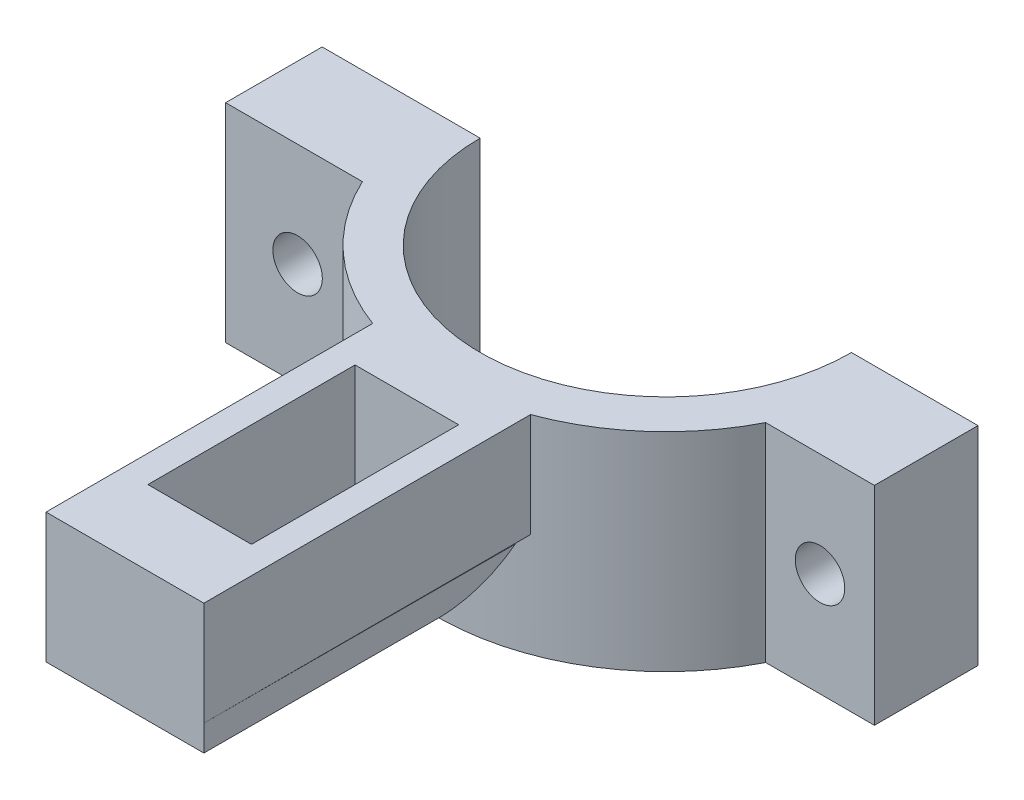
SolidWorks part; units mm, degrees
ref_plane "前基準面" through (0, 0, 0) normal (0, 0, 1) x (1, 0, 0)
ref_plane "上基準面" through (0, 0, 0) normal (0, 1, 0) x (1, 0, 0)
ref_plane "右基準面" through (0, 0, 0) normal (1, 0, 0) x (0, 0, -1)
sketch "草圖1" plane through (0, 0, 0) normal (0, 1, 0) x (1, 0, 0)
  circle A0 centre (0, 0) radius 14.34
  dimension "D1" = 28.68
extrude "伸長-薄件1" add sketch "草圖1" along normal blind 16.05 thin thin type one direction wall 3.29
ref_plane "平面1" through (17.75, 0, 0) normal (1, 0, 0) x (0, 0, -1)
sketch "草圖2" plane through (17.75, 0, 0) normal (1, 0, 0) x (0, 0, -1)
  line L0 (0, -983.95) -> (0, 49016.05) construction
  line L1 (14.34, 16.05) -> (-14.34, 16.05) construction
  line L2 (-1017.63, 8.025) -> (48982.37, 8.025) construction
  line L3 (-17.63, 16.05) -> (-17.63, 0) construction
  line L5 (-8, 16.05) -> (8, 16.05)
  line L6 (-8, 16.05) -> (-8, 0)
  line L7 (-8, 0) -> (8, 0)
  line L8 (8, 16.05) -> (8, 0)
  line L9 (-8, 16.05) -> (8, 0) construction
  line L10 (-8, 0) -> (8, 16.05) construction
  point P5 (0, 16.05)
  point P6 (0, 8.025)
  point P10 (-17.63, 8.025)
  dimension "D1" = 0
  dimension "D2" = 16
extrude "填料-伸長1" add sketch "草圖2" along normal blind 9.77 and the other way blind 3
sketch "草圖3" plane through (0, 16.05, 0) normal (0, 1, 0) x (1, 0, 0)
  line L0 (14.34, 0) -> (27.52, 0) construction
  line L1 (27.52, 8) -> (27.52, -8) construction
  line L2 (15.7104, -8) -> (27.52, -8) construction
  line L3 (27.52, 8) -> (24.11, 8)
  line L4 (27.52, 8) -> (27.52, -8)
  line L5 (27.52, -8) -> (24.11, -8)
  line L6 (24.11, 8) -> (24.11, -8)
  circle A0 centre (0, 0) radius 14.34 construction
  dimension "D1" = 3.41
extrude "除料-伸長1" cut sketch "草圖3" against normal through all
sketch "草圖4" plane through (0, 0, 8) normal (0, 0, 1) x (1, 0, 0)
  line L0 (19.9102, -983.95) -> (19.9102, 49016.05) construction
  line L1 (15.7104, 16.05) -> (24.11, 16.05) construction
  line L2 (-984.2896, 8.025) -> (49015.7104, 8.025) construction
  line L3 (15.7104, 0) -> (15.7104, 16.05) construction
  circle A0 centre (19.9102, 8.025) radius 1.91
  point P5 (19.9102, 16.05)
  point P10 (15.7104, 8.025)
  dimension "D1" = 3.82
extrude "除料-伸長2" cut sketch "草圖4" against normal through all
ref_plane "平面2" through (0, 0, 17.75) normal (0, 0, 1) x (1, 0, 0)
sketch "草圖5" plane through (0, 0, 17.75) normal (0, 0, 1) x (1, 0, 0)
  line L0 (-1017.63, 8.025) -> (48982.37, 8.025) construction
  line L1 (-17.63, 16.05) -> (-17.63, 0) construction
  line L2 (0, -983.95) -> (0, 49016.05) construction
  line L3 (14.34, 16.05) -> (-14.34, 16.05) construction
  line L5 (-6.095, 16.2886) -> (6.095, 16.2886)
  line L6 (-6.095, 16.2886) -> (-6.095, 8.025)
  line L7 (-6.095, 8.025) -> (6.095, 8.025)
  line L8 (6.095, 16.2886) -> (6.095, 8.025)
  line L9 (-6.095, 16.2886) -> (6.095, 8.025) construction
  line L10 (-6.095, 8.025) -> (6.095, 16.2886) construction
  point P5 (-17.63, 8.025)
  point P6 (0, 12.1568)
  point P10 (0, 16.05)
  dimension "D1" = 12.19
extrude "填料-伸長2" add sketch "草圖5" along normal blind 4 and the other way blind 2.77
sketch "草圖6" plane through (0, 16.2886, 0) normal (0, 1, 0) x (1, 0, 0)
  line L1 (-6.095, -14.98) -> (6.095, -14.98)
  line L2 (-6.095, -14.98) -> (-6.095, -21.75)
  line L3 (-6.095, -21.75) -> (6.095, -21.75)
  line L4 (6.095, -14.98) -> (6.095, -21.75)
extrude "填料-伸長3" add sketch "草圖6" along normal blind 63
sketch "草圖8" plane through (0, 79.2886, 0) normal (0, 1, 0) x (1, 0, 0)
  line L1 (-6.095, -21.75) -> (6.095, -21.75)
  line L2 (-6.095, -21.75) -> (-6.095, -14.98)
  line L3 (-6.095, -14.98) -> (6.095, -14.98)
  line L4 (6.095, -21.75) -> (6.095, -14.98)
extrude "填料-伸長4" add sketch "草圖8" along normal blind 0.16
ref_plane "平面3" through (-17.75, 0, 0) normal (1, 0, 0) x (0, 0, -1)
sketch "草圖12" plane through (-17.75, 0, 0) normal (1, 0, 0) x (0, 0, -1)
  line L0 (0.5435, -983.95) -> (0.5435, 49016.05) construction
  line L1 (17.63, 16.05) -> (-16.5429, 16.05) construction
  line L2 (-982.37, 8.025) -> (49017.63, 8.025) construction
  line L3 (17.63, 0) -> (17.63, 16.05) construction
  line L5 (8.5435, 16.05) -> (-7.4565, 16.05)
  line L6 (8.5435, 16.05) -> (8.5435, 0)
  line L7 (8.5435, 0) -> (-7.4565, 0)
  line L8 (-7.4565, 16.05) -> (-7.4565, 0)
  line L9 (8.5435, 16.05) -> (-7.4565, 0) construction
  line L10 (8.5435, 0) -> (-7.4565, 16.05) construction
  point P5 (0.5435, 16.05)
  point P6 (0.5435, 8.025)
  point P10 (17.63, 8.025)
  dimension "D1" = 0
  dimension "D2" = 16
extrude "填料-伸長5" add sketch "草圖12" along normal blind 3.16 and the other way blind 10
sketch "草圖13" plane through (0, 16.05, 0) normal (0, 1, 0) x (1, 0, 0)
  line L0 (-14.34, 0) -> (-27.75, 0) construction
  line L1 (-27.75, 8.5435) -> (-27.75, -7.4565) construction
  line L2 (-27.75, -7.4565) -> (-15.9755, -7.4565) construction
  line L3 (-27.75, 8.5435) -> (-26.54, 8.5435)
  line L4 (-27.75, 8.5435) -> (-27.75, -7.4565)
  line L5 (-27.75, -7.4565) -> (-26.54, -7.4565)
  line L6 (-26.54, 8.5435) -> (-26.54, -7.4565)
  circle A0 centre (0, 0) radius 14.34 construction
  dimension "D1" = 1.21
extrude "除料-伸長3" cut sketch "草圖13" against normal through all
sketch "草圖14" plane through (0, 0, -8.5435) normal (0, 0, -1) x (-1, 0, 0)
  line L0 (20.9808, -983.95) -> (20.9808, 49016.05) construction
  line L1 (26.54, 16.05) -> (15.4216, 16.05) construction
  line L2 (-973.46, 8.025) -> (49026.54, 8.025) construction
  line L3 (26.54, 0) -> (26.54, 16.05) construction
  circle A0 centre (20.9808, 8.025) radius 1.91
  point P5 (20.9808, 16.05)
  point P10 (26.54, 8.025)
  dimension "D1" = 3.82
extrude "除料-伸長4" cut sketch "草圖14" against normal through all
sketch "草圖15" plane through (0, 79.4486, 0) normal (0, 1, 0) x (1, 0, 0)
  line L0 (6.095, -14.98) -> (-6.095, -14.98) construction
  circle A0 centre (0, -14.98) radius 4.05
  dimension "D1" = 8.1
extrude "除料-伸長5" cut sketch "草圖15" against normal blind 24
sketch "草圖16" plane through (0, 16.05, 0) normal (0, 1, 0) x (1, 0, 0)
  line L0 (24.11, 8) -> (24.11, -8) construction
  line L1 (24.11, 0) -> (-32.2905, 0)
  line L2 (24.11, 0) -> (24.11, 19.935)
  line L3 (24.11, 19.935) -> (-32.2905, 19.935)
  line L4 (-32.2905, 0) -> (-32.2905, 19.935)
extrude "除料-伸長6" cut sketch "草圖16" against normal through all
sketch "草圖17" plane through (0, 0, 21.75) normal (0, 0, 1) x (1, 0, 0)
  line L1 (-6.095, 8.025) -> (6.095, 8.025)
  line L2 (-6.095, 8.025) -> (-6.095, 79.4486)
  line L3 (-6.095, 79.4486) -> (6.095, 79.4486)
  line L4 (6.095, 8.025) -> (6.095, 79.4486)
extrude "填料-伸長7" add sketch "草圖17" along normal blind 25
sketch "草圖18" plane through (-6.095, 0, 0) normal (-1, 0, 0) x (0, 0, 1)
  line L0 (14.98, 79.4486) -> (46.75, 79.4486) construction
  line L1 (14.98, 16.05) -> (41.7734, 16.05)
  line L2 (14.98, 16.05) -> (14.98, 79.4486)
  line L3 (14.98, 79.4486) -> (41.7734, 79.4486)
  line L4 (41.7734, 16.05) -> (41.7734, 79.4486)
extrude "除料-伸長7" cut sketch "草圖18" against normal blind 25
sketch "草圖19" plane through (0, 79.4486, 0) normal (0, 1, 0) x (1, 0, 0)
  line L0 (6.095, -41.7734) -> (-6.095, -41.7734) construction
  circle A0 centre (0, -41.7734) radius 4
  dimension "D1" = 8
extrude "除料-伸長8" cut sketch "草圖19" against normal blind 24
sketch "草圖20" plane through (6.095, 0, 0) normal (1, 0, 0) x (0, 0, -1)
  line L0 (-41.7734, 16.05) -> (-41.7734, 8.025)
  line L1 (-16.5429, 8.025) -> (-46.75, 8.025) construction
  line L2 (-41.7734, 8.025) -> (-46.75, 8.025)
  line L3 (-46.75, 8.025) -> (-46.75, 79.4486)
  line L4 (-46.75, 79.4486) -> (-41.7734, 79.4486)
  line L5 (-41.7734, 79.4486) -> (-41.7734, 16.05)
extrude "除料-伸長9" cut sketch "草圖20" against normal blind 29
sketch "草圖21" plane through (0, 16.05, 0) normal (0, 1, 0) x (1, 0, 0)
  line L0 (0, -1014.34) -> (0, 48985.66) construction
  line L2 (-4, -20) -> (4, -20)
  line L3 (-4, -20) -> (-4, -36)
  line L4 (-4, -36) -> (4, -36)
  line L5 (4, -20) -> (4, -36)
  line L6 (-4, -20) -> (4, -36) construction
  line L7 (-4, -36) -> (4, -20) construction
  arc A0 (-14.34, 0) -> (14.34, 0) centre (0, 0) ccw construction
  point P1 (0, -28)
  point P6 (0, -14.34)
  dimension "D1" = 20
  dimension "D2" = 16
  dimension "D3" = 8
extrude "除料-伸長10" cut sketch "草圖21" against normal blind 8
sketch "草圖23" plane through (0, 8.025, 0) normal (0, -1, 0) x (1, 0, 0)
  line L0 (-6.095, 41.7734) -> (-6.095, 17.75)
  line L1 (8.8275, 17.75) -> (-8.8275, 17.75) construction
  line L2 (-6.095, 16.5429) -> (-6.095, 41.7734) construction
  line L3 (-6.095, 17.75) -> (6.1383, 17.75)
  line L4 (6.1383, 17.75) -> (6.095, 41.7734)
  line L5 (6.095, 41.7734) -> (-6.095, 41.7734)
extrude "填料-伸長9" add sketch "草圖23" along normal blind 2
fillet "圓角1" radius 10 1 edges at (0.0216, 6.025, 17.75)
